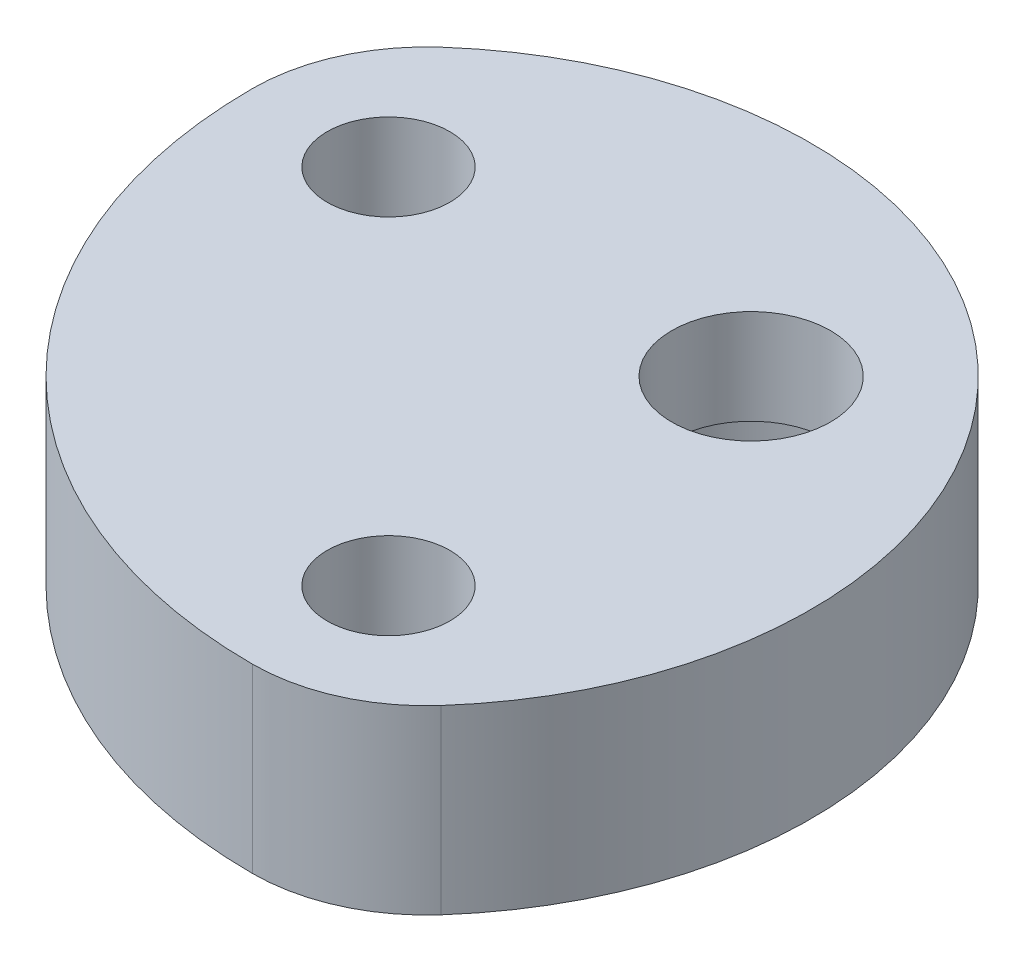
SolidWorks part; units mm, degrees
ref_plane "Front" through (0, 0, 0) normal (0, 0, 1) x (1, 0, 0)
ref_plane "Top" through (0, 0, 0) normal (0, 1, 0) x (1, 0, 0)
ref_plane "Right" through (0, 0, 0) normal (1, 0, 0) x (0, 0, -1)
ref_axis "side-side" through (80.9, 0, 0) along (-1, 0, 0)
ref_axis "up-down" through (0, 50, 0) along (0, -1, 0)
ref_axis "front-back" through (0, 0, -80.9) along (0, 0, 1)
sketch "Sketch1" plane through (0, 0, 0) normal (0, 1, 0) x (1, 0, 0)
  line L0 (-11, 0) -> (-11, -5.8816) construction
  line L1 (0, -11) -> (-7.0863, -11) construction
  line L2 (0, 0) -> (2.506, 2.506) construction
  line L3 (2.506, 2.506) -> (-6.8149, 11.8269) construction
  line L6 (5.5829, -4.328) -> (-11.0454, -5.2768) construction
  arc A0 (2.506, 2.506) -> (2.8668, -9.7121) centre (-3.7945, -3.7945) cw
  arc A1 (2.8668, -9.7121) -> (0, -11) centre (0, -7.1653) cw
  circle A2 centre (0, 0) radius 3.044
  circle A3 centre (0, 0) radius 3.044 construction
  arc A4 (2.506, 2.506) -> (-9.7121, 2.8668) centre (-3.7945, -3.7945) ccw
  arc A5 (-9.7121, 2.8668) -> (-11, 0) centre (-7.1653, 0) ccw
  circle A6 centre (0, 0) radius 3.544 construction
  circle A7 centre (0, 0) radius 11 construction
  circle A8 centre (0, 0) radius 11 construction
  arc A9 (0, -11) -> (-11, 0) centre (0, 0) cw
  dimension "D3" = 7.956
  dimension "D4" = 45
  dimension "D5" = 8.9102
  dimension "D1" = 0.25
  dimension "D2" = 0.5
extrude "Boss-Extrude1" add sketch "Sketch1" along normal blind 4
hole_wizard "#6-32 Tapped Hole1" positions "Sketch2" profile "Sketch3" tap size "#6-32" standard "ANSI Inch" end condition through all
sketch "Sketch2" plane through (0, 0, 0) normal (0, -1, 0) x (-1, 0, 0)
  point P0 (8, 0)
  point P3 (0, -8)
cosmetic thread "Hole Thread1" parameters "D2"=3.5052
cosmetic thread "Hole Thread2" parameters "D2"=3.5052
sketch "Sketch3" plane through (-8, 0, 0) normal (1, 0, 0) x (0, 0, -1)
  line L0 (0, 0) -> (0, 4)
  line L1 (0, 4) -> (1.3525, 4)
  line L2 (1.3525, 4) -> (1.3525, 0)
  line L5 (1.3525, 0) -> (0, 0)
  line L11 (0, -6.35) -> (0, 107.95) construction
  dimension "Thru Tap Drill Dia." = 2.7051
  dimension "Thru Tap Drill Depth" = 4
sketch "Sketch4" plane through (0, 0, 0) normal (0, -1, 0) x (1, 0, 0)
  circle A0 centre (0, 0) radius 3.044 construction
  circle A1 centre (0, 0) radius 3.044
extrude "Cut-Extrude1" cut sketch "Sketch4" against normal blind 1.905
sketch "Sketch5" plane through (0, 1.905, 0) normal (0, -1, 0) x (1, 0, 0)
  circle A0 centre (0, 0) radius 1.75
  dimension "D1" = 3.5
extrude "Cut-Extrude2" cut sketch "Sketch5" against normal through all
